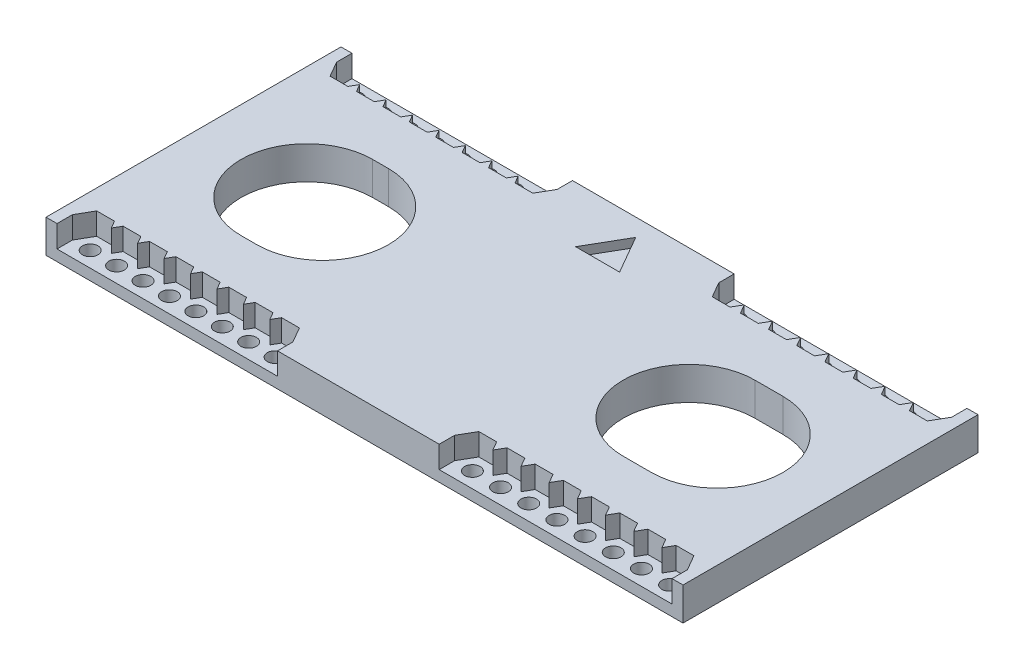
SolidWorks part; units mm, degrees
note: The reader was unsure of these and kept them because the rebuilt part matched: shared geometry of "Sketch1<5>".
ref_plane "Front Plane" through (0, 0, 0) normal (0, 0, 1) x (1, 0, 0)
ref_plane "Top Plane" through (0, 0, 0) normal (0, 1, 0) x (1, 0, 0)
ref_plane "Right Plane" through (0, 0, 0) normal (1, 0, 0) x (0, 0, -1)
sketch "Sketch1" plane through (0, 0, 0) normal (0, 1, 0) x (1, 0, 0)
  line L0 (0, 38.1) -> (0, -38.1) construction
  line L1 (150.876, 38.1) -> (159.004, -38.1) construction
  line L2 (-5.0555, 33.6582) -> (-3.81, 35.8155)
  line L3 (-5.0555, 33.6582) -> (172.6955, 33.6582)
  line L4 (-5.0555, 33.6582) -> (-5.0555, 0)
  line L5 (-5.0555, 0) -> (172.6955, 0)
  line L6 (172.6955, 33.6582) -> (172.6955, 0)
  line L7 (-3.81, 35.8155) -> (-2.5645, 33.6582)
  line L8 (0, 38.1) -> (-3.8467, 35.8791) construction
  line L9 (0, 38.1) -> (3.81, 38.1) construction
  line L10 (3.81, 38.1) -> (7.62, 38.1) construction
  line L11 (7.62, 38.1) -> (7.62, 33.6582) construction
  line L12 (0, 38.1) -> (-3.81, 38.1) construction
  line L13 (2.5645, 33.6582) -> (3.81, 35.8155)
  line L14 (3.81, 35.8155) -> (5.0555, 33.6582)
  line L15 (10.1845, 33.6582) -> (11.43, 35.8155)
  line L16 (11.43, 35.8155) -> (12.6755, 33.6582)
  line L17 (17.8045, 33.6582) -> (19.05, 35.8155)
  line L18 (19.05, 35.8155) -> (20.2955, 33.6582)
  line L19 (25.4245, 33.6582) -> (26.67, 35.8155)
  line L20 (26.67, 35.8155) -> (27.9155, 33.6582)
  line L21 (33.0445, 33.6582) -> (34.29, 35.8155)
  line L22 (34.29, 35.8155) -> (35.5355, 33.6582)
  line L23 (40.6645, 33.6582) -> (41.91, 35.8155)
  line L24 (41.91, 35.8155) -> (43.1555, 33.6582)
  line L25 (48.2845, 33.6582) -> (49.53, 35.8155)
  line L26 (49.53, 35.8155) -> (50.7755, 33.6582)
  line L27 (55.9045, 33.6582) -> (57.15, 35.8155)
  line L28 (57.15, 35.8155) -> (58.3955, 33.6582)
  line L29 (-3.81, 35.8155) -> (3.81, 35.8155) construction
  line L30 (7.62, 38.1) -> (15.24, 38.1) construction
  line L31 (172.6955, 33.6582) -> (171.196, 36.2554)
  line L32 (171.196, 36.2554) -> (169.6965, 33.6582)
  line L33 (167.132, 38.1) -> (170.9787, 35.8791) construction
  line L34 (167.132, 38.1) -> (171.196, 38.1) construction
  line L35 (167.132, 38.1) -> (163.068, 38.1) construction
  line L36 (163.068, 38.1) -> (159.004, 38.1) construction
  line L37 (164.5675, 33.6582) -> (163.068, 36.2554)
  line L38 (163.068, 36.2554) -> (161.5685, 33.6582)
  line L39 (156.4395, 33.6582) -> (154.94, 36.2554)
  line L40 (154.94, 36.2554) -> (153.4405, 33.6582)
  line L41 (148.3115, 33.6582) -> (146.812, 36.2554)
  line L42 (146.812, 36.2554) -> (145.3125, 33.6582)
  line L43 (140.1835, 33.6582) -> (138.684, 36.2554)
  line L44 (138.684, 36.2554) -> (137.1845, 33.6582)
  line L45 (132.0555, 33.6582) -> (130.556, 36.2554)
  line L46 (130.556, 36.2554) -> (129.0565, 33.6582)
  line L47 (123.9275, 33.6582) -> (122.428, 36.2554)
  line L48 (122.428, 36.2554) -> (120.9285, 33.6582)
  line L49 (115.7995, 33.6582) -> (114.3, 36.2554)
  line L50 (114.3, 36.2554) -> (112.8005, 33.6582)
  line L51 (107.6715, 33.6582) -> (106.172, 36.2554)
  line L52 (106.172, 36.2554) -> (104.6725, 33.6582)
  line L53 (-8.304, 42.5418) -> (175.436, 42.5418)
  line L54 (15.24, 42.5418) -> (15.24, 33.6582) construction
  line L55 (-5.129, 42.5418) -> (-5.129, 38.1)
  line L56 (-8.304, 42.5418) -> (-8.304, 0)
  line L58 (171.196, 36.2554) -> (172.261, 38.1)
  line L59 (172.261, 38.1) -> (172.261, 42.5418)
  line L60 (172.6955, 0) -> (175.436, 0)
  line L61 (-5.0555, 0) -> (-8.304, 0)
  line L62 (57.15, 35.8155) -> (58.469, 38.1)
  line L63 (58.469, 38.1) -> (58.469, 42.5418)
  line L64 (106.172, 36.2554) -> (105.107, 38.1)
  line L65 (105.107, 38.1) -> (105.107, 42.5418)
  line L66 (175.436, 42.5418) -> (175.436, 0)
  line L67 (-5.129, 38.1) -> (-3.8467, 35.8791)
  line L68 (-3.8467, 35.8791) -> (-3.81, 35.8155)
  circle A0 centre (0, 38.1) radius 2.2479
  circle A1 centre (0, -38.1) radius 2.2479 construction
  circle A2 centre (7.62, 38.1) radius 2.2479
  circle A3 centre (7.62, -38.1) radius 2.2479 construction
  circle A4 centre (15.24, 38.1) radius 2.2479
  circle A5 centre (15.24, -38.1) radius 2.2479 construction
  circle A6 centre (22.86, 38.1) radius 2.2479
  circle A7 centre (22.86, -38.1) radius 2.2479 construction
  circle A8 centre (30.48, 38.1) radius 2.2479
  circle A9 centre (30.48, -38.1) radius 2.2479 construction
  circle A10 centre (38.1, 38.1) radius 2.2479
  circle A11 centre (38.1, -38.1) radius 2.2479 construction
  circle A12 centre (45.72, 38.1) radius 2.2479
  circle A13 centre (45.72, -38.1) radius 2.2479 construction
  circle A14 centre (53.34, 38.1) radius 2.2479
  circle A15 centre (53.34, -38.1) radius 2.2479 construction
  circle A16 centre (110.236, 38.1) radius 2.2479
  circle A17 centre (110.236, -38.1) radius 2.2479 construction
  circle A18 centre (118.364, 38.1) radius 2.2479
  circle A19 centre (118.364, -38.1) radius 2.2479 construction
  circle A20 centre (126.492, 38.1) radius 2.2479
  circle A21 centre (126.492, -38.1) radius 2.2479 construction
  circle A22 centre (134.62, 38.1) radius 2.2479
  circle A23 centre (134.62, -38.1) radius 2.2479 construction
  circle A24 centre (142.748, 38.1) radius 2.2479
  circle A25 centre (142.748, -38.1) radius 2.2479 construction
  circle A26 centre (150.876, 38.1) radius 2.2479
  circle A27 centre (150.876, -38.1) radius 2.2479 construction
  circle A28 centre (159.004, 38.1) radius 2.2479
  circle A29 centre (159.004, -38.1) radius 2.2479 construction
  circle A30 centre (167.132, 38.1) radius 2.2479
  circle A31 centre (167.132, -38.1) radius 2.2479 construction
  circle A32 centre (15.24, 0) radius 19
  circle A34 centre (15.24, 0) radius 23.544
  point P4 (0, 0)
  point P79 (3.81, 38.1)
  dimension "D1" = 76.2
  dimension "D2" = 4.4958
  dimension "D5" = 8
  dimension "D8" = 38
  dimension "D15" = 3.175
  dimension "D4" = 7.62
  dimension "D6" = 8.128
  dimension "D7" = 111.76
  dimension "D9" = 4.4418
  dimension "D10" = 120
  dimension "D11" = 9
  dimension "D12" = 120
  dimension "D13" = 9
  dimension "D16" = 3.175
  dimension "D3" = 8
extrude "Boss-Extrude1" add sketch "Sketch1" against normal blind 9.525
extrude "Cut-Extrude1" cut sketch "Sketch1<5>" against normal blind 6.35
sketch "Sketch1<5>" plane through (0, 0, 0) normal (0, 1, 0) x (1, 0, 0) same geometry as "Sketch1"
mirror "Mirror1" about plane through (0, 0, 0) normal (0, 0, 1) of bodies 102
sketch "Sketch2" plane through (0, 0, 0) normal (0, 1, 0) x (1, 0, 0)
  line L0 (142.748, 0) -> (134.62, 0) construction
  line L1 (24.384, 0) -> (28.956, 0) construction
  line L3 (142.748, 0) -> (134.62, 0) construction
  line L4 (142.748, -19) -> (134.62, -19)
  line L5 (142.748, 19) -> (134.62, 19)
  line L6 (28.956, 0) -> (24.384, 0) construction
  line L7 (28.956, -19) -> (24.384, -19)
  line L8 (28.956, 19) -> (24.384, 19)
  arc A2 (142.748, -19) -> (142.748, 19) centre (142.748, 0) ccw
  arc A3 (134.62, 19) -> (134.62, -19) centre (134.62, 0) ccw
  arc A4 (28.956, -19) -> (28.956, 19) centre (28.956, 0) ccw
  arc A5 (24.384, 19) -> (24.384, -19) centre (24.384, 0) ccw
  circle A6 centre (15.24, 0) radius 19 construction
  point P5 (110.236, 38.1)
  point P6 (167.132, 38.1)
  point P8 (53.34, 38.1)
  point P9 (0, 38.1)
  point P12 (138.684, 0)
  point P21 (26.67, 0)
  dimension "D1" = 24.384
  dimension "D2" = 24.384
  dimension "D3" = 24.384
  dimension "D4" = 24.384
extrude "Cut-Extrude2" cut sketch "Sketch2" against normal through all
sketch "Sketch4" plane through (0, 0, 0) normal (0, 1, 0) x (1, 0, 0)
  line L0 (75.438, 26.4633) -> (81.788, 37.4618)
  line L1 (81.788, 37.4618) -> (88.138, 26.4633)
  line L2 (88.138, 26.4633) -> (75.438, 26.4633)
  line L3 (58.469, 42.5418) -> (105.107, 42.5418) construction
  point P3 (81.788, 42.5418)
  dimension "D1" = 12.7
  dimension "D2" = 5.08
extrude "Cut-Extrude3" cut sketch "Sketch4" against normal blind 2.54
